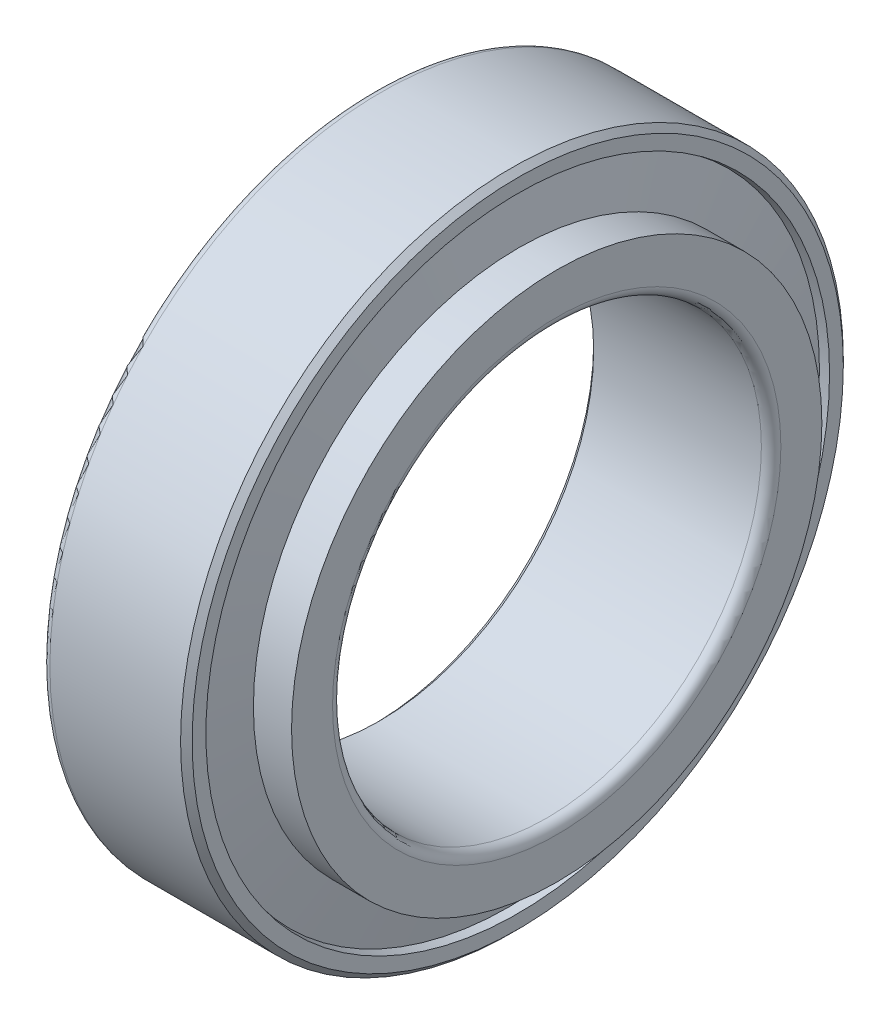
SolidWorks part; units mm, degrees
revolve "OuterRace" add sketch "OutRacSke" angle 360 about L5 other way angle 28.04 reverse direction yes
sketch "OutRacSke" plane through (0, 0, 0) normal (0, 0, 1) x (1, 0, 0)
  line L0 (-10, 79.99) -> (-47, 73.1325)
  line L1 (-47, 73.1325) -> (-47, 83)
  line L2 (-45, 85) -> (-11.48, 85)
  line L3 (-11.48, 85) -> (-10, 83.52)
  line L4 (-10, 83.52) -> (-10, 79.99)
  line L5 (-42.5, 0) -> (42.5, 0) construction
  arc A0 (-47, 83) -> (-45, 85) centre (-45, 83) cw
  dimension "D8" = 45
  dimension "Tangle" = 10.5
ref_plane "Plane1" through (0, 0, 0) normal (0, 0, 1) x (1, 0, 0)
ref_plane "Plane2" through (0, 0, 0) normal (0, 1, 0) x (1, 0, 0)
ref_plane "Plane3" through (0, 0, 0) normal (1, 0, 0) x (0, 0, -1)
sketch "Clipboard" plane through (0, 0, 0) normal (0, 0, 1) x (1, 0, 0)
  line L0 (0, 0) -> (10, 0) construction
  line L1 (0, 0) -> (146.1759, -5.1046)
  line L2 (0, 0) -> (109.933, 3.8389)
  line L3 (0, 0) -> (169.8964, -5.9329)
  line L4 (0, 0) -> (-33.2949, -0.5812)
  line L5 (0, 0) -> (-13.5, 47)
  dimension "Roller_diameter" = 13.5
  dimension "cyl_len" = 33.3
sketch "RolDetSke" plane through (0, 0, 0) normal (0, 0, 1) x (1, 0, 0)
  line L0 (-43.7699, 67.2337) -> (-45, 73.8707)
  line L1 (-43.7699, 67.2337) -> (-11.0275, 73.3022)
  line L2 (-12.2576, 79.9391) -> (-11.0275, 73.3022)
  line L4 (-50.3965, 66.0056) -> (0.1359, 75.3712) construction
  line L5 (-12.2576, 79.9391) -> (-45, 73.8707)
  line L9 (-10, 79.99) -> (-47, 73.1325) construction
  dimension "Roller_diameter" = 13.5
  dimension "dy" = 73.8707
  dimension "D2" = 45
  dimension "cyl_len" = 33.3
revolve "RollerDetailed" [suppressed] add sketch "RolDetSke" angle 360 about L4 reverse direction yes
sketch "RolSimSke" plane through (0, 0, 0) normal (0, 0, 1) x (1, 0, 0)
  line L0 (0, 0) -> (-32, 0) construction
  line L1 (-45, 73.8707) -> (-12.2576, 79.9391)
  line L2 (-45, 73.8707) -> (-42.5398, 60.5968)
  line L3 (-42.5398, 60.5968) -> (-9.7974, 66.6652)
  line L4 (-12.2576, 79.9391) -> (-9.7974, 66.6652)
  dimension "Roller_diameter" = 13.5
  dimension "dy" = 73.8707
  dimension "dx" = 45
  dimension "Tangle" = 10.5
revolve "RollersSimplified" add sketch "RolSimSke" angle 360 about L0
ref_axis "Axis1" through (-50, 0, 0) along (1, 0, 0)
pattern_circular "RollersDetailed" [suppressed] count 2 every 180 about axis through (-50, 0, 0) along (1, 0, 0)
sketch "InsRacSke" plane through (0, 0, 0) normal (0, 0, 1) x (1, 0, 0)
  line L0 (-42.6526, 61.2718) -> (-47, 61.2718)
  line L1 (-47, 83) -> (-47, -83) construction
  line L2 (-47, 61.2718) -> (-47, 56.48)
  line L3 (-47, 56.48) -> (-45.52, 55)
  line L4 (-45.52, 55) -> (-2.5, 55)
  line L5 (0, 57.5) -> (0, 68.0152)
  line L6 (0, 68.0152) -> (-9.7851, 68.0152)
  line L7 (-9.7851, 68.0152) -> (-9.7851, 66.6652)
  line L8 (-9.7851, 66.6652) -> (-42.5275, 60.5968)
  line L9 (-42.5275, 60.5968) -> (-42.6526, 61.2718)
  line L10 (-42.5, 0) -> (42.5, 0) construction
  arc A0 (-2.5, 55) -> (0, 57.5) centre (-2.5, 57.5) ccw
  dimension "Tangle" = 10.5
  dimension "cyl_len" = 33.3
  dimension "dy" = 60.5968
  dimension "dx" = 42.5275
  dimension "D11" = 45
  dimension "D2" = 47
revolve "InnerRace" add sketch "InsRacSke" angle 360 about L10 reverse direction yes
sketch "CagSpiSke" plane through (0, 0, 0) normal (0, 0, 1) x (1, 0, 0)
  line L3 (-9.3904, 73.2381) -> (-43.7699, 66.8662)
  line L4 (-44.4908, 65.8173) -> (-44.1628, 64.0474)
  line L6 (-42.5, 0) -> (42.5, 0) construction
  arc A1 (-43.7699, 66.8662) -> (-44.4908, 65.8173) centre (-43.6059, 65.9813) ccw
  dimension "Tangle" = 10.5
  dimension "radius" = 0.9
  dimension "dx" = 43.7699
  dimension "dy" = 66.8662
  dimension "offset" = 2.7
revolve "CageSpine" [suppressed] add sketch "CagSpiSke" angle 0.001 about L6 wall 2.25
equation "\"OD@OutRacSke\" = \"Race_OD@Clipboard\""
equation "\"cup_SID@OutRacSke\" = \"Race_ID@Clipboard\""
equation "\"chamfer@OutRacSke\" = \"cup_width@OutRacSke\" / 25"
equation "\"offset@OutRacSke\" = \"OA_width@Clipboard\""
equation "\"D2@RolDetSke\" = \"offset@OutRacSke\" - \"cup_radius@OutRacSke\""
equation "\"dy@RolDetSke\" =  ( ( \"Race_ID@Clipboard\" / 2 ) + ( \"cup_radius@OutRacSke\" ) * tan(\"Tangle@OutRacSke\" * 3.141592654/180) ) * 1.005"
equation "\"cyl_len@RolDetSke\" = \"cyl_len@Clipboard\""
equation "\"Roller_diameter@RolDetSke\" = \"Roller_diameter@Clipboard\""
equation "\"dx@RolSimSke\" = \"offset@OutRacSke\" - \"cup_radius@OutRacSke\""
equation "\"dy@RolSimSke\" =  ( ( \"Race_ID@Clipboard\" / 2 ) + ( \"cup_radius@OutRacSke\" ) * tan(\"Tangle@OutRacSke\" * 3.141592654/180) ) * 1.005"
equation "\"Cyl_Len@RolSimSke\" = \"cyl_len@Clipboard\""
equation "\"Roller_diameter@RolSimSke\" = \"Roller_diameter@Clipboard\""
equation "\"Bore@InsRacSke\" = \"Bore@Clipboard\""
equation "\"Tangle@InsRacSke\" = \"Tangle@OutRacSke\""
equation "\"cyl_len@InsRacSke\" = \"cyl_len@Clipboard\""
equation "\"chamfer@InsRacSke\" = \"chamfer@OutRacSke\""
equation "\"D2@InsRacSke\" = \"OA_width@Clipboard\""
equation "\"dx@InsRacSke\" = \"offset@OutRacSke\" - \"cup_radius@OutRacSke\" -  (  \"Roller_diameter@Clipboard\" * 1.005 )  * sin(\"Tangle@InsRacSke\" * 3.141592654/180)"
equation "\"dy@InsRacSke\" = ( ( \"Race_ID@Clipboard\" / 2 ) + ( \"cup_radius@OutRacSke\" ) * tan(\"Tangle@OutRacSke\" * 3.141592654/180) ) * 1.005 -  ( \"Roller_diameter@Clipboard\" )  * cos(\"Tangle@InsRacSke\" * 3.141592654/180) "
equation "\"front_groove@InsRacSke\" = \"Groove_dp@InsRacSke\" / 2"
equation "\"Tangle@CagSpiSke\" = \"Tangle@OutRacSke\""
equation "\"dx@CagSpiSke\" = ( \"offset@OutRacSke\" - \"cup_radius@OutRacSke\" ) -  (  \"Roller_diameter@Clipboard\" / 2  )  * sin(\"Tangle@InsRacSke\" * 3.141592654/180)"
equation "\"dy@CagSpiSke\" = ( ( \"Race_ID@Clipboard\" / 2 ) + ( \"cup_radius@OutRacSke\" ) * tan(\"Tangle@OutRacSke\" * 3.141592654/180) )  -  ( \"Roller_diameter@Clipboard\" / 2 )  * cos(\"Tangle@InsRacSke\" * 3.141592654/180) "
equation "\"length@CagSpiSke\" = \"cyl_len@Clipboard\" * 1.05"
equation "\"offset@CagSpiSke\" = \"Roller_diameter@Clipboard\" / 5"
equation "\"radius@CagSpiSke\" = \"offset@CagSpiSke\" / 3"
equation "\"D3@CageSpine\" = \"Roller_diameter@Clipboard\" / 6"
equation "\"Max_count@Clipboard\" = int( 3.14159265 / atn(( \"Roller_diameter@Clipboard\" / 2) / sqr( \"dy@CagSpiSke\"  *  \"dy@CagSpiSke\" - ( \"Roller_diameter@Clipboard\" / 2) *  ( \"Roller_diameter@Clipboard\" / 2))))"
equation "\"Max_count@Clipboard\" = ((sgn( \"Max_count@Clipboard\" - \"Count@Clipboard\" )-1)*( \"Max_count@Clipboard\" - \"Count@Clipboard\" ))/-2+ \"Count@Clipboard\""
equation "\"Count@RollersDetailed\" = int( \"Show_count@Clipboard\" ) "
equation "\"Count@RollersDetailed\" = ((sgn( \"Count@RollersDetailed\" - \"Max_count@Clipboard\" )-1)*( \"Count@RollersDetailed\" - \"Max_count@Clipboard\" ))/-2+ \"Max_count@Clipboard\""
equation "\"Count@RollersDetailed\" = ((sgn( \"Count@RollersDetailed\" - \"Min_count@Clipboard\" )+1)*( \"Count@RollersDetailed\" - \"Min_count@Clipboard\"))/2 +\"Min_count@Clipboard\""
equation "\"Angle@RollersDetailed\" = 360.0 / \"Max_count@Clipboard\""
equation "\"Angle@CageSpine\" =  \"Angle@RollersDetailed\" * ( \"Count@RollersDetailed\" -1 + int( \"Count@RollersDetailed\" / \"Max_count@Clipboard\" ) )  + 0.001 -  int( \"Count@RollersDetailed\" / \"Max_count@Clipboard\" ) * 0.001"
equation "\"Angle@CageSpine\" =  \"Angle@CageSpine\" * int( \"Min_count@Clipboard\" / 2) + int(1 / \"Min_count@Clipboard\")  * 0.001"
equation "\"Tangle@RolSimSke\" = \"Tangle@OutRacSke\""
